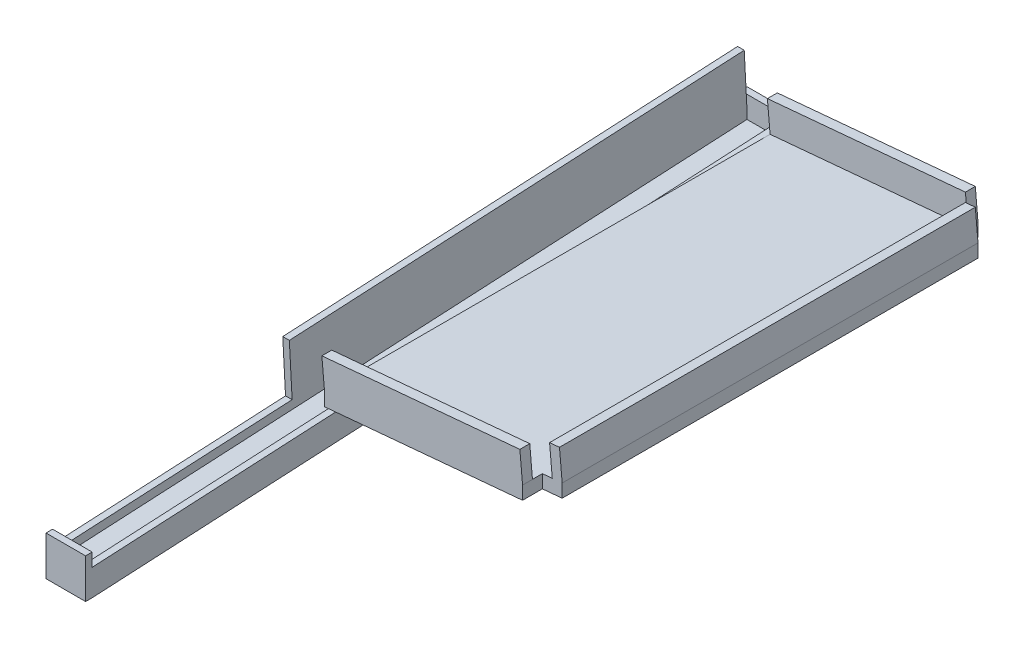
SolidWorks part; units mm, degrees
ref_plane "Front Plane" through (0, 0, 0) normal (0, 0, 1) x (1, 0, 0)
ref_plane "Top Plane" through (0, 0, 0) normal (0, 1, 0) x (1, 0, 0)
ref_plane "Right Plane" through (0, 0, 0) normal (1, 0, 0) x (0, 0, -1)
sketch "Sketch1" plane through (0, 0, 0) normal (0, 0, 1) x (1, 0, 0)
  line L0 (0, 0) -> (0, 20)
  line L1 (0, 0) -> (330, 0)
  line L2 (330, 0) -> (330, 50)
  line L3 (330, 50) -> (0, 20)
  line L4 (0, 0) -> (330, 30)
  dimension "D1" = 20
  dimension "D2" = 20
  dimension "D3" = 330
  dimension "D4" = 50
extrude "Boss-Extrude1" add sketch "Sketch1" along normal blind 690 contours L0 L4 L2 L3 region at (165, 25, 0)
sketch "Sketch3" plane through (0, 0, 0) normal (0, 1, 0) x (1, 0, 0)
  line L0 (300, -690) -> (330, -690)
  line L1 (330, -690) -> (330, -660)
  line L2 (330, -30) -> (330, 0)
  line L3 (330, -690) -> (300, -690)
  line L4 (330, -690) -> (330, -660)
  line L5 (330, -660) -> (300, -660)
  line L6 (300, -690) -> (300, -660)
  line L7 (330, 0) -> (300, 0)
  line L8 (330, 0) -> (330, -30)
  line L9 (330, -30) -> (300, -30)
  line L10 (300, 0) -> (300, -30)
  dimension "D2" = 30
  dimension "D3" = 30
  dimension "D4" = 30
  dimension "D5" = 30
  dimension "D6" = 690
extrude "Cut-Extrude2" cut sketch "Sketch3" along normal through all contours L6 L0 L1 L5 | L7 L10 L9 L2 region at (315, 0, 675) region at (315, 0, 15)
sketch "Sketch4" plane through (0, 0, 0) normal (-1, 0, 0) x (0, 0, 1)
  line L0 (0, 20) -> (0, 0)
  line L1 (1042, -34.6089) -> (1042, -54.6089)
  line L3 (0, 20) -> (1042, -34.6089)
  line L4 (1042, -54.6089) -> (1042, -74.6089)
  line L5 (1042, -74.6089) -> (0, -20)
  line L6 (0, -20) -> (0, 0)
  point P1 (986.3594, -41.3686)
  point P8 (0, 0)
  dimension "D1" = 40
  dimension "D2" = 20
  dimension "D3" = 40
  dimension "D4" = 87
  dimension "D5" = 1042
extrude "Boss-Extrude2" add sketch "Sketch4" along normal blind 60
sketch "Sketch6" plane through (0, 19.9452, 1.0453) normal (0, 0.9986, 0.0523) x (1, 0, 0)
  line L1 (-60, 1.0467) -> (0, 1.0467) construction
  line L2 (-50, 1.0467) -> (-50, -1042.3833)
  line L3 (-60, -1042.3833) -> (0, -1042.3833) construction
  line L4 (-50, -1042.3833) -> (-10, -1042.3833)
  line L5 (-10, -1042.3833) -> (-10, 1.0467)
  line L6 (-10, 1.0467) -> (-50, 1.0467)
  dimension "D1" = 10
  dimension "D2" = 10
extrude "Cut-Extrude3" cut sketch "Sketch6" against normal blind 13
sketch "Sketch7" plane through (0, -54.5541, 1040.9547) normal (0, 0.0523, -0.9986) x (-1, 0, 0)
  line L0 (10, 6.9726) -> (10, 19.9726)
  line L1 (10, 19.9726) -> (50, 19.9726)
  line L2 (50, 19.9726) -> (50, 6.9726)
  line L3 (50, 6.9726) -> (10, 6.9726)
extrude "Cut-Extrude4" cut sketch "Sketch7" against normal through all
sketch "Sketch8" plane through (0, 19.9452, 1.0453) normal (0, 0.9986, 0.0523) x (1, 0, 0)
  line L1 (-60, 1.0467) -> (-50, 1.0467)
  line L2 (-60, 1.0467) -> (-60, -689.0232)
  line L3 (-60, -689.0232) -> (-50, -689.0232)
  line L4 (-50, 1.0467) -> (-50, -689.0232)
  point P5 (-60, 1.0467)
  dimension "D1" = 690.0699
sketch "Sketch10" plane through (0, 0, 1042) normal (0, 0, 1) x (1, 0, 0)
  line L10 (-60, -14.6089) -> (0, -14.6089)
  line L11 (-60, -14.6089) -> (-60, -74.6089)
  line L12 (-60, -74.6089) -> (0, -74.6089)
  line L13 (0, -14.6089) -> (0, -74.6089)
  dimension "D1" = 60
extrude "Boss-Extrude4" add sketch "Sketch10" along normal blind 10
ref_plane "Plane1" through (0, -80, 0) normal (0, 1, 0) x (1, 0, 0)
sketch "Sketch16" plane through (-60, 0, 0) normal (-1, 0, 0) x (0, 0, 1)
  line L0 (0, -20) -> (0, -80)
  line L1 (214.5, -80) -> (-214.5, -80) construction
  line L2 (0, -80) -> (30, -80)
  line L3 (30, -80) -> (30, -21.5722)
  line L4 (0, -20) -> (1042, -74.6089) construction
  line L5 (521, -47.3045) -> (521, -80)
  line L6 (521, -80) -> (551, -80)
  line L7 (551, -80) -> (551, -48.8767)
  line L8 (521, -47.3045) -> (551, -48.8767)
  line L9 (0, -20) -> (30, -21.5722)
  dimension "D1" = 30
  dimension "D2" = 30
extrude "Boss-Extrude8" add sketch "Sketch16" against normal blind 30
sketch "Sketch17" plane through (-1.8033, 19.8361, 0) normal (-0.0905, 0.9959, 0) x (0.9959, 0.0905, 0)
  line L0 (1.8107, -690) -> (1.8107, 0) construction
  line L1 (1.8107, -15) -> (303.0478, -15)
  line L2 (1.8107, -15) -> (1.8107, 0)
  line L3 (1.8107, 0) -> (303.0478, 0)
  line L4 (303.0478, -15) -> (303.0478, 0)
  line L6 (333.1715, -30) -> (318.1097, -30)
  line L7 (333.1715, -30) -> (333.1715, -660)
  line L8 (333.1715, -660) -> (318.1097, -660)
  line L9 (318.1097, -30) -> (318.1097, -660)
  line L10 (303.0478, -690) -> (303.0478, -660) construction
  line L11 (303.0478, -675) -> (1.8107, -675)
  line L12 (303.0478, -675) -> (303.0478, -690)
  line L13 (303.0478, -690) -> (1.8107, -690)
  line L14 (1.8107, -675) -> (1.8107, -690)
  line L15 (303.0478, 0) -> (303.0478, -30) construction
  line L17 (333.1715, -30) -> (303.0478, -30) construction
  point P11 (0, 0)
  point P12 (0, 0)
  point P21 (273.3367, -15)
  point P24 (0, 0)
  point P25 (0, 0)
  point P26 (0, 0)
  point P27 (0, 0)
  point P29 (0, 0)
  point P30 (387.5771, -660)
  point P31 (387.5771, -660)
  point P35 (318.1097, -30)
extrude "Boss-Extrude9" add sketch "Sketch17" along normal blind 45
extrude "Boss-Extrude10" add sketch "Sketch8" along normal blind 80 contours L4 L3 L2 L1
sketch "Sketch21" plane through (0, 0, 0) normal (0, 0, -1) x (-1, 0, 0)
  line L0 (60, 99.8904) -> (60, 20) construction
  line L1 (0, -20) -> (60, -20)
  line L2 (0, -20) -> (0, 40)
  line L3 (0, 40) -> (60, 40)
  line L4 (60, -20) -> (60, 40)
  dimension "D1" = 60
extrude "Boss-Extrude14" add sketch "Sketch21" along normal blind 10 separate body
